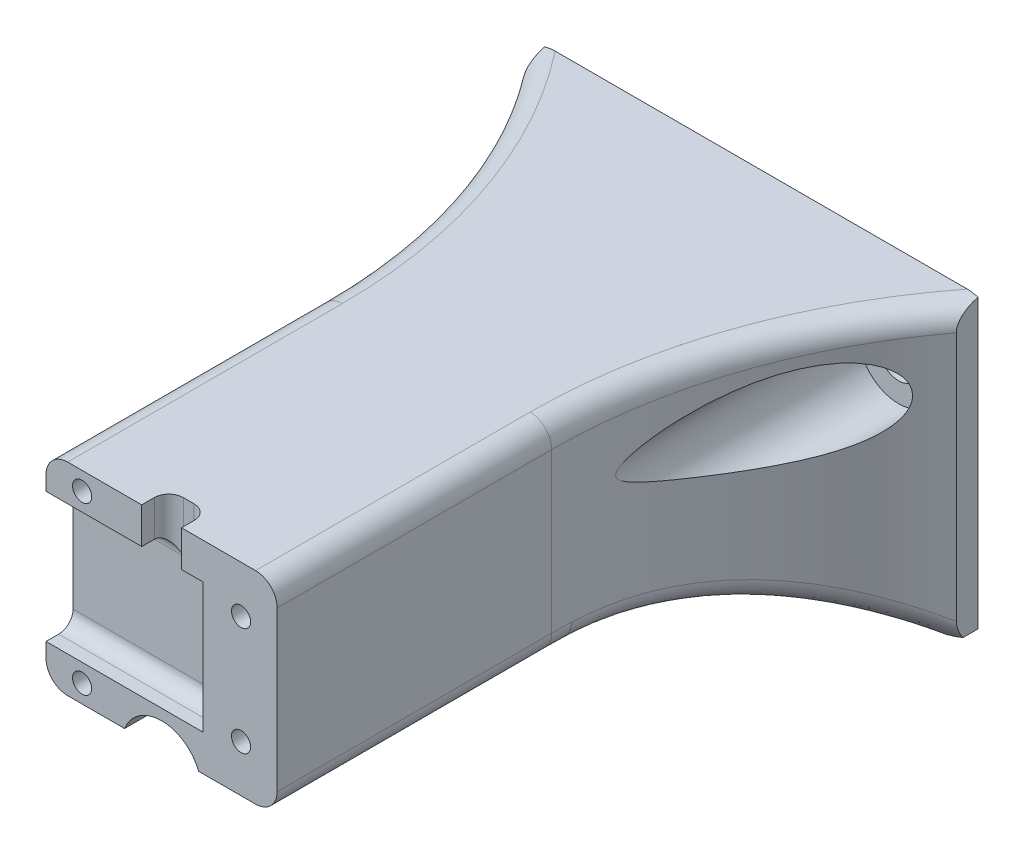
SolidWorks part; units mm, degrees
ref_plane "Front Plane" through (0, 0, 0) normal (0, 0, 1) x (1, 0, 0)
ref_plane "Top Plane" through (0, 0, 0) normal (0, 1, 0) x (1, 0, 0)
ref_plane "Right Plane" through (0, 0, 0) normal (1, 0, 0) x (0, 0, -1)
sketch "Sketch1" plane through (0, 0, 0) normal (0, 0, 1) x (1, 0, 0)
  line L0 (8, 10) -> (52, 10) construction
  line L1 (0, 0) -> (60, 0)
  line L2 (0, 0) -> (0, 40)
  line L3 (0, 40) -> (60, 40)
  line L4 (60, 0) -> (60, 40)
  line L5 (8, 30) -> (52, 30) construction
  circle A0 centre (52, 30) radius 2.75
  circle A1 centre (8, 30) radius 2.75
  circle A2 centre (30, 10) radius 2.75 construction
  point P7 (30, 0)
  point P8 (30, 10)
  point P11 (30, 30)
  dimension "D6" = 5.5
  dimension "D1" = 40
  dimension "D2" = 60
  dimension "D3" = 44
  dimension "D4" = 10
  dimension "D5" = 20
extrude "Boss-Extrude1" add sketch "Sketch1" along normal blind 3
sketch "Sketch2" plane through (0, 0, 3) normal (0, 0, 1) x (1, 0, 0)
  line L0 (60, 40) -> (0, 40) construction
  line L1 (14, 40) -> (46, 40)
  line L2 (14, 40) -> (14, 12)
  line L3 (14, 12) -> (46, 12)
  line L4 (46, 40) -> (46, 12)
  point P6 (30, 40)
  point P7 (30, 40)
  dimension "D1" = 28
  dimension "D2" = 32
extrude "Boss-Extrude2" add sketch "Sketch2" along normal blind 80
sketch "Sketch3" plane through (0, 0, 83) normal (0, 0, 1) x (1, 0, 0)
  line L0 (46, 40) -> (14, 40) construction
  line L1 (27.25, 40) -> (32.75, 40)
  line L2 (27.25, 40) -> (27.25, 35)
  line L4 (32.75, 40) -> (32.75, 35)
  line L5 (14, 12) -> (46, 12) construction
  line L6 (5.75, 35) -> (27.25, 35)
  line L7 (5.75, 35) -> (5.75, 17)
  line L8 (5.75, 17) -> (35.75, 17)
  line L9 (35.75, 35) -> (35.75, 17)
  line L10 (32.75, 35) -> (35.75, 35)
  point P6 (30, 40)
  point P7 (30, 40)
  point P12 (0, 0)
  point P13 (35.75, 18.0525)
  dimension "D1" = 5.5
  dimension "D2" = 18
  dimension "D3" = 30
  dimension "D4" = 3
  dimension "D5" = 5
  dimension "D6" = 5
extrude "Cut-Extrude1" cut sketch "Sketch3" against normal blind 3.75
sketch "Sketch4" plane through (0, 0, 83) normal (0, 0, 1) x (1, 0, 0)
  line L0 (41, 33.5) -> (41, 18.5) construction
  line L1 (46, 12) -> (46, 40) construction
  line L2 (19, 37.5) -> (19, 14.5) construction
  line L3 (27.25, 40) -> (14, 40) construction
  line L4 (14, 12) -> (46, 12) construction
  line L5 (14, 17) -> (14, 12) construction
  circle A0 centre (41, 33.5) radius 1.325
  circle A1 centre (41, 18.5) radius 1.325
  circle A2 centre (19, 37.5) radius 1.325
  circle A3 centre (19, 14.5) radius 1.325
  point P6 (46, 26)
  point P7 (41, 26)
  point P12 (19.8776, 35.705)
  dimension "D1" = 2.65
  dimension "D2" = 5
  dimension "D3" = 15
  dimension "D4" = 2.5
  dimension "D5" = 2.5
  dimension "D6" = 5
extrude "Cut-Extrude2" cut sketch "Sketch4" against normal blind 8
fillet "Fillet1" radius 2 5 edges at (27.25, 37.5, 79.25) (24.875, 17, 79.25) (34.25, 35, 79.25) (20.625, 35, 79.25) (32.75, 37.5, 79.25)
fillet "Fillet2" radius 70 3 edges at (46, 26, 3) (14, 26, 3) (30, 12, 3)
fillet "Fillet3" radius 3 10 edges at (46, 12, 64) (14, 12, 64) (46, 40, 64) (14, 40, 64) (49.2813, 9.546, 23.8196) (10.7039, 9.5333, 23.7729) (49.5922, 40, 22.8641) (10.4078, 40, 22.8641) (46.0141, 12, 43.5956) (13.9859, 12, 43.5956)
sketch "Sketch5" plane through (0, 0, 0) normal (0, 0, -1) x (-1, 0, 0)
  circle A0 centre (-52, 30) radius 5.5
  circle A1 centre (-8, 30) radius 5.5
  circle A2 centre (-30, 10) radius 5.5
  point P9 (0, 0)
  dimension "D1" = 11
extrude "Cut-Extrude3" cut sketch "Sketch5" against normal through all from offset 3 offset against normal yes
sketch "Sketch6" plane through (0, 0, 0) normal (0, 0, -1) x (-1, 0, 0)
  circle A0 centre (-30, 10) radius 2.75
  arc A1 (-35.1235, 12) -> (-24.8765, 12) centre (-30, 10) ccw construction
  dimension "D1" = 5.5
extrude "Cut-Extrude4" cut sketch "Sketch6" against normal through all
